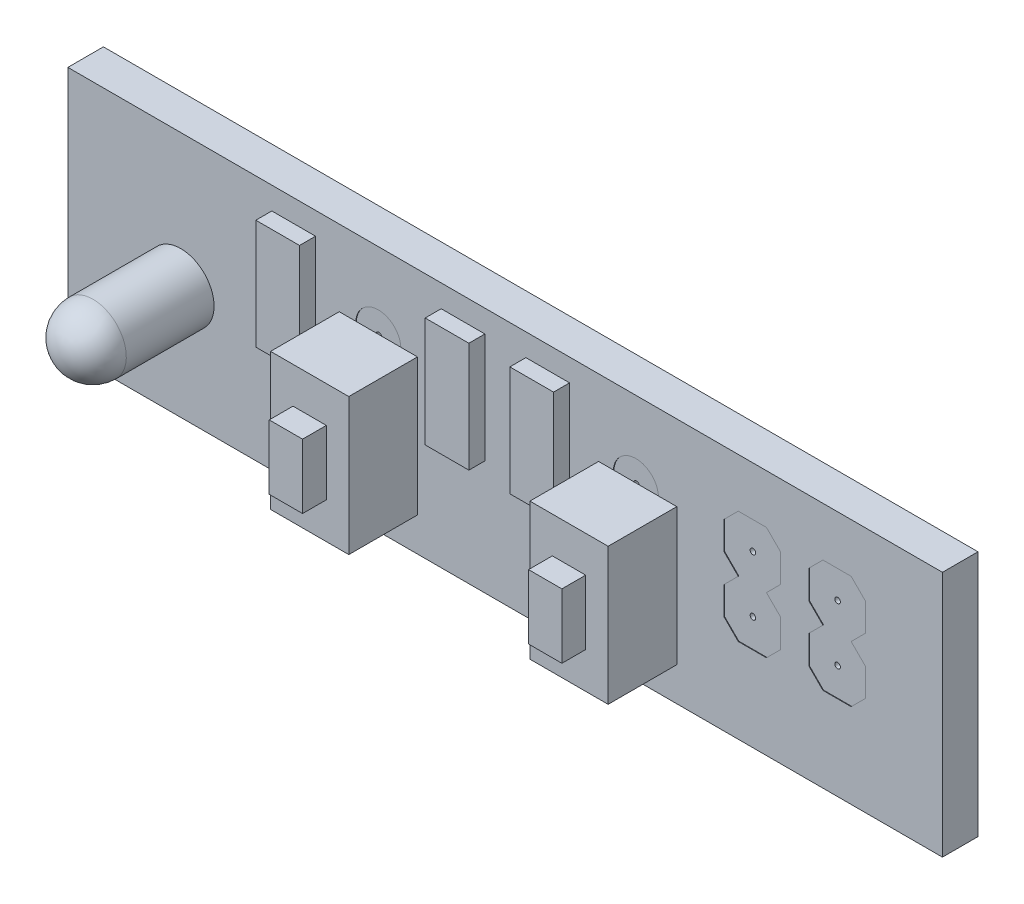
SolidWorks part; units mm, degrees
ref_plane "Front Plane" through (0, 0, 0) normal (0, 0, 1) x (1, 0, 0)
ref_plane "Top Plane" through (0, 0, 0) normal (0, 1, 0) x (1, 0, 0)
ref_plane "Right Plane" through (0, 0, 0) normal (1, 0, 0) x (0, 0, -1)
sketch "Model" plane through (0, 0, 0) normal (0, 0, 1) x (1, 0, 0)
  line L0 (0, 0) -> (39.35, 0)
  line L1 (39.35, 0) -> (39.35, 11.1)
  line L2 (39.35, 11.1) -> (0, 11.1)
  line L3 (0, 11.1) -> (0, 0)
  line L4 (26.7811, 0.4445) -> (26.7811, 0.9525)
  line L5 (26.7811, 0.4445) -> (26.2731, 0.4445)
  line L6 (26.7811, 2.2225) -> (26.7811, 2.7305)
  line L7 (26.7811, 2.7305) -> (26.2731, 2.7305)
  line L8 (25.0031, 2.7305) -> (24.4951, 2.7305)
  line L9 (24.4951, 2.7305) -> (24.4951, 2.2225)
  line L10 (24.4951, 0.9525) -> (24.4951, 0.4445)
  line L11 (24.4951, 0.4445) -> (25.0031, 0.4445)
  line L12 (15.113, 0.4445) -> (15.113, 0.9525)
  line L13 (15.113, 0.4445) -> (14.605, 0.4445)
  line L14 (15.113, 2.2225) -> (15.113, 2.7305)
  line L15 (15.113, 2.7305) -> (14.605, 2.7305)
  line L16 (13.335, 2.7305) -> (12.827, 2.7305)
  line L17 (12.827, 2.7305) -> (12.827, 2.2225)
  line L18 (12.827, 0.9525) -> (12.827, 0.4445)
  line L19 (12.827, 0.4445) -> (13.335, 0.4445)
  line L20 (26.7018, 6.477) -> (26.7018, 6.985)
  line L21 (26.7018, 6.477) -> (26.1938, 6.477)
  line L22 (26.7018, 8.255) -> (26.7018, 8.763)
  line L23 (26.7018, 8.763) -> (26.1938, 8.763)
  line L24 (24.9238, 8.763) -> (24.4158, 8.763)
  line L25 (24.4158, 8.763) -> (24.4158, 8.255)
  line L26 (24.4158, 6.985) -> (24.4158, 6.477)
  line L27 (24.4158, 6.477) -> (24.9238, 6.477)
  line L28 (15.113, 6.477) -> (15.113, 6.985)
  line L29 (15.113, 6.477) -> (14.605, 6.477)
  line L30 (15.113, 8.255) -> (15.113, 8.763)
  line L31 (15.113, 8.763) -> (14.605, 8.763)
  line L32 (13.335, 8.763) -> (12.827, 8.763)
  line L33 (12.827, 8.763) -> (12.827, 8.255)
  line L34 (12.827, 6.985) -> (12.827, 6.477)
  line L35 (12.827, 6.477) -> (13.335, 6.477)
  line L36 (29.5275, 4.445) -> (29.5275, 5.715)
  line L37 (29.5275, 5.715) -> (30.1625, 6.35)
  line L38 (30.1625, 6.35) -> (31.4325, 6.35)
  line L39 (31.4325, 6.35) -> (32.0675, 5.715)
  line L40 (30.1625, 3.81) -> (31.4325, 3.81)
  line L41 (29.5275, 4.445) -> (30.1625, 3.81)
  line L42 (31.4325, 3.81) -> (32.0675, 4.445)
  line L43 (32.0675, 5.715) -> (32.0675, 4.445)
  line L44 (30.1625, 6.35) -> (29.5275, 6.985)
  line L45 (29.5275, 6.985) -> (29.5275, 8.255)
  line L46 (29.5275, 8.255) -> (30.1625, 8.89)
  line L47 (30.1625, 8.89) -> (31.4325, 8.89)
  line L48 (31.4325, 8.89) -> (32.0675, 8.255)
  line L49 (32.0675, 8.255) -> (32.0675, 6.985)
  line L50 (32.0675, 6.985) -> (31.4325, 6.35)
  line L51 (33.3375, 4.445) -> (33.3375, 5.715)
  line L52 (33.3375, 5.715) -> (33.9725, 6.35)
  line L53 (33.9725, 6.35) -> (35.2425, 6.35)
  line L54 (35.2425, 6.35) -> (35.8775, 5.715)
  line L55 (33.9725, 3.81) -> (35.2425, 3.81)
  line L56 (33.3375, 4.445) -> (33.9725, 3.81)
  line L57 (35.2425, 3.81) -> (35.8775, 4.445)
  line L58 (35.8775, 5.715) -> (35.8775, 4.445)
  line L59 (33.9725, 6.35) -> (33.3375, 6.985)
  line L60 (33.3375, 6.985) -> (33.3375, 8.255)
  line L61 (33.3375, 8.255) -> (33.9725, 8.89)
  line L62 (33.9725, 8.89) -> (35.2425, 8.89)
  line L63 (35.2425, 8.89) -> (35.8775, 8.255)
  line L64 (35.8775, 8.255) -> (35.8775, 6.985)
  line L65 (35.8775, 6.985) -> (35.2425, 6.35)
  line L66 (3.5052, 6.35) -> (3.5052, 3.81)
  line L69 (9.177, 5.147) -> (9.177, 10.093)
  line L70 (9.177, 10.093) -> (11.143, 10.093)
  line L71 (11.143, 10.093) -> (11.143, 5.147)
  line L72 (11.143, 5.147) -> (9.177, 5.147)
  line L75 (18.763, 10.093) -> (18.763, 5.147)
  line L76 (18.763, 5.147) -> (16.797, 5.147)
  line L77 (16.797, 5.147) -> (16.797, 10.093)
  line L78 (16.797, 10.093) -> (18.763, 10.093)
  line L79 (22.4028, 8.5725) -> (22.4028, 6.6548)
  line L80 (20.7772, 8.5725) -> (20.7772, 6.6548)
  line L81 (20.607, 5.147) -> (20.607, 10.093)
  line L82 (20.607, 10.093) -> (22.573, 10.093)
  line L83 (22.573, 10.093) -> (22.573, 5.147)
  line L84 (22.573, 5.147) -> (20.607, 5.147)
  arc A0 (26.8192, 0.9525) -> (26.743, 0.9525) centre (26.7811, 0.9525) ccw
  arc A1 (26.743, 0.4445) -> (26.8192, 0.4445) centre (26.7811, 0.4445) ccw
  arc A2 (26.2731, 0.4826) -> (26.2731, 0.4064) centre (26.2731, 0.4445) ccw
  arc A3 (26.7811, 0.4064) -> (26.7811, 0.4826) centre (26.7811, 0.4445) ccw
  arc A4 (26.8192, 2.7305) -> (26.743, 2.7305) centre (26.7811, 2.7305) ccw
  arc A5 (26.743, 2.2225) -> (26.8192, 2.2225) centre (26.7811, 2.2225) ccw
  arc A6 (26.2731, 2.7686) -> (26.2731, 2.6924) centre (26.2731, 2.7305) ccw
  arc A7 (26.7811, 2.6924) -> (26.7811, 2.7686) centre (26.7811, 2.7305) ccw
  arc A8 (24.4951, 2.7686) -> (24.4951, 2.6924) centre (24.4951, 2.7305) ccw
  arc A9 (25.0031, 2.6924) -> (25.0031, 2.7686) centre (25.0031, 2.7305) ccw
  arc A10 (24.457, 2.2225) -> (24.5332, 2.2225) centre (24.4951, 2.2225) ccw
  arc A11 (24.5332, 2.7305) -> (24.457, 2.7305) centre (24.4951, 2.7305) ccw
  arc A12 (24.457, 0.4445) -> (24.5332, 0.4445) centre (24.4951, 0.4445) ccw
  arc A13 (24.5332, 0.9525) -> (24.457, 0.9525) centre (24.4951, 0.9525) ccw
  arc A14 (25.0031, 0.4064) -> (25.0031, 0.4826) centre (25.0031, 0.4445) ccw
  arc A15 (24.4951, 0.4826) -> (24.4951, 0.4064) centre (24.4951, 0.4445) ccw
  circle A16 centre (25.6381, 1.5875) radius 1.016
  arc A17 (15.1511, 0.9525) -> (15.0749, 0.9525) centre (15.113, 0.9525) ccw
  arc A18 (15.0749, 0.4445) -> (15.1511, 0.4445) centre (15.113, 0.4445) ccw
  arc A19 (14.605, 0.4826) -> (14.605, 0.4064) centre (14.605, 0.4445) ccw
  arc A20 (15.113, 0.4064) -> (15.113, 0.4826) centre (15.113, 0.4445) ccw
  arc A21 (15.1511, 2.7305) -> (15.0749, 2.7305) centre (15.113, 2.7305) ccw
  arc A22 (15.0749, 2.2225) -> (15.1511, 2.2225) centre (15.113, 2.2225) ccw
  arc A23 (14.605, 2.7686) -> (14.605, 2.6924) centre (14.605, 2.7305) ccw
  arc A24 (15.113, 2.6924) -> (15.113, 2.7686) centre (15.113, 2.7305) ccw
  arc A25 (12.827, 2.7686) -> (12.827, 2.6924) centre (12.827, 2.7305) ccw
  arc A26 (13.335, 2.6924) -> (13.335, 2.7686) centre (13.335, 2.7305) ccw
  arc A27 (12.7889, 2.2225) -> (12.8651, 2.2225) centre (12.827, 2.2225) ccw
  arc A28 (12.8651, 2.7305) -> (12.7889, 2.7305) centre (12.827, 2.7305) ccw
  arc A29 (12.7889, 0.4445) -> (12.8651, 0.4445) centre (12.827, 0.4445) ccw
  arc A30 (12.8651, 0.9525) -> (12.7889, 0.9525) centre (12.827, 0.9525) ccw
  arc A31 (13.335, 0.4064) -> (13.335, 0.4826) centre (13.335, 0.4445) ccw
  arc A32 (12.827, 0.4826) -> (12.827, 0.4064) centre (12.827, 0.4445) ccw
  circle A33 centre (13.97, 1.5875) radius 1.016
  arc A34 (26.7399, 6.985) -> (26.6637, 6.985) centre (26.7018, 6.985) ccw
  arc A35 (26.6637, 6.477) -> (26.7399, 6.477) centre (26.7018, 6.477) ccw
  arc A36 (26.1938, 6.5151) -> (26.1938, 6.4389) centre (26.1938, 6.477) ccw
  arc A37 (26.7018, 6.4389) -> (26.7018, 6.5151) centre (26.7018, 6.477) ccw
  arc A38 (26.7399, 8.763) -> (26.6637, 8.763) centre (26.7018, 8.763) ccw
  arc A39 (26.6637, 8.255) -> (26.7399, 8.255) centre (26.7018, 8.255) ccw
  arc A40 (26.1938, 8.8011) -> (26.1938, 8.7249) centre (26.1938, 8.763) ccw
  arc A41 (26.7018, 8.7249) -> (26.7018, 8.8011) centre (26.7018, 8.763) ccw
  arc A42 (24.4158, 8.8011) -> (24.4158, 8.7249) centre (24.4158, 8.763) ccw
  arc A43 (24.9238, 8.7249) -> (24.9238, 8.8011) centre (24.9238, 8.763) ccw
  arc A44 (24.3777, 8.255) -> (24.4539, 8.255) centre (24.4158, 8.255) ccw
  arc A45 (24.4539, 8.763) -> (24.3777, 8.763) centre (24.4158, 8.763) ccw
  arc A46 (24.3777, 6.477) -> (24.4539, 6.477) centre (24.4158, 6.477) ccw
  arc A47 (24.4539, 6.985) -> (24.3777, 6.985) centre (24.4158, 6.985) ccw
  arc A48 (24.9238, 6.4389) -> (24.9238, 6.5151) centre (24.9238, 6.477) ccw
  arc A49 (24.4158, 6.5151) -> (24.4158, 6.4389) centre (24.4158, 6.477) ccw
  circle A50 centre (25.5587, 7.62) radius 1.016
  arc A51 (15.1511, 6.985) -> (15.0749, 6.985) centre (15.113, 6.985) ccw
  arc A52 (15.0749, 6.477) -> (15.1511, 6.477) centre (15.113, 6.477) ccw
  arc A53 (14.605, 6.5151) -> (14.605, 6.4389) centre (14.605, 6.477) ccw
  arc A54 (15.113, 6.4389) -> (15.113, 6.5151) centre (15.113, 6.477) ccw
  arc A55 (15.1511, 8.763) -> (15.0749, 8.763) centre (15.113, 8.763) ccw
  arc A56 (15.0749, 8.255) -> (15.1511, 8.255) centre (15.113, 8.255) ccw
  arc A57 (14.605, 8.8011) -> (14.605, 8.7249) centre (14.605, 8.763) ccw
  arc A58 (15.113, 8.7249) -> (15.113, 8.8011) centre (15.113, 8.763) ccw
  arc A59 (12.827, 8.8011) -> (12.827, 8.7249) centre (12.827, 8.763) ccw
  arc A60 (13.335, 8.7249) -> (13.335, 8.8011) centre (13.335, 8.763) ccw
  arc A61 (12.7889, 8.255) -> (12.8651, 8.255) centre (12.827, 8.255) ccw
  arc A62 (12.8651, 8.763) -> (12.7889, 8.763) centre (12.827, 8.763) ccw
  arc A63 (12.7889, 6.477) -> (12.8651, 6.477) centre (12.827, 6.477) ccw
  arc A64 (12.8651, 6.985) -> (12.7889, 6.985) centre (12.827, 6.985) ccw
  arc A65 (13.335, 6.4389) -> (13.335, 6.5151) centre (13.335, 6.477) ccw
  arc A66 (12.827, 6.5151) -> (12.827, 6.4389) centre (12.827, 6.477) ccw
  circle A67 centre (13.97, 7.62) radius 1.016
  arc A68 (29.5656, 5.715) -> (29.4894, 5.715) centre (29.5275, 5.715) ccw
  arc A69 (29.4894, 4.445) -> (29.5656, 4.445) centre (29.5275, 4.445) ccw
  arc A70 (30.1894, 6.3231) -> (30.1356, 6.3769) centre (30.1625, 6.35) ccw
  arc A71 (29.5006, 5.7419) -> (29.5544, 5.6881) centre (29.5275, 5.715) ccw
  arc A72 (31.4325, 6.3119) -> (31.4325, 6.3881) centre (31.4325, 6.35) ccw
  arc A73 (30.1625, 6.3881) -> (30.1625, 6.3119) centre (30.1625, 6.35) ccw
  arc A74 (32.0406, 5.6881) -> (32.0944, 5.7419) centre (32.0675, 5.715) ccw
  arc A75 (31.4594, 6.3769) -> (31.4056, 6.3231) centre (31.4325, 6.35) ccw
  arc A76 (31.4325, 3.7719) -> (31.4325, 3.8481) centre (31.4325, 3.81) ccw
  arc A77 (30.1625, 3.8481) -> (30.1625, 3.7719) centre (30.1625, 3.81) ccw
  arc A78 (30.1356, 3.7831) -> (30.1894, 3.8369) centre (30.1625, 3.81) ccw
  arc A79 (29.5544, 4.4719) -> (29.5006, 4.4181) centre (29.5275, 4.445) ccw
  arc A80 (32.0944, 4.4181) -> (32.0406, 4.4719) centre (32.0675, 4.445) ccw
  arc A81 (31.4056, 3.8369) -> (31.4594, 3.7831) centre (31.4325, 3.81) ccw
  arc A82 (32.0294, 4.445) -> (32.1056, 4.445) centre (32.0675, 4.445) ccw
  arc A83 (32.1056, 5.715) -> (32.0294, 5.715) centre (32.0675, 5.715) ccw
  arc A84 (29.5544, 7.0119) -> (29.5006, 6.9581) centre (29.5275, 6.985) ccw
  arc A85 (30.1356, 6.3231) -> (30.1894, 6.3769) centre (30.1625, 6.35) ccw
  arc A86 (29.5656, 8.255) -> (29.4894, 8.255) centre (29.5275, 8.255) ccw
  arc A87 (29.4894, 6.985) -> (29.5656, 6.985) centre (29.5275, 6.985) ccw
  arc A88 (30.1894, 8.8631) -> (30.1356, 8.9169) centre (30.1625, 8.89) ccw
  arc A89 (29.5006, 8.2819) -> (29.5544, 8.2281) centre (29.5275, 8.255) ccw
  arc A90 (31.4325, 8.8519) -> (31.4325, 8.9281) centre (31.4325, 8.89) ccw
  arc A91 (30.1625, 8.9281) -> (30.1625, 8.8519) centre (30.1625, 8.89) ccw
  arc A92 (32.0406, 8.2281) -> (32.0944, 8.2819) centre (32.0675, 8.255) ccw
  arc A93 (31.4594, 8.9169) -> (31.4056, 8.8631) centre (31.4325, 8.89) ccw
  arc A94 (32.0294, 6.985) -> (32.1056, 6.985) centre (32.0675, 6.985) ccw
  arc A95 (32.1056, 8.255) -> (32.0294, 8.255) centre (32.0675, 8.255) ccw
  arc A96 (31.4056, 6.3769) -> (31.4594, 6.3231) centre (31.4325, 6.35) ccw
  arc A97 (32.0944, 6.9581) -> (32.0406, 7.0119) centre (32.0675, 6.985) ccw
  arc A98 (33.3756, 5.715) -> (33.2994, 5.715) centre (33.3375, 5.715) ccw
  arc A99 (33.2994, 4.445) -> (33.3756, 4.445) centre (33.3375, 4.445) ccw
  arc A100 (33.9994, 6.3231) -> (33.9456, 6.3769) centre (33.9725, 6.35) ccw
  arc A101 (33.3106, 5.7419) -> (33.3644, 5.6881) centre (33.3375, 5.715) ccw
  arc A102 (35.2425, 6.3119) -> (35.2425, 6.3881) centre (35.2425, 6.35) ccw
  arc A103 (33.9725, 6.3881) -> (33.9725, 6.3119) centre (33.9725, 6.35) ccw
  arc A104 (35.8506, 5.6881) -> (35.9044, 5.7419) centre (35.8775, 5.715) ccw
  arc A105 (35.2694, 6.3769) -> (35.2156, 6.3231) centre (35.2425, 6.35) ccw
  arc A106 (35.2425, 3.7719) -> (35.2425, 3.8481) centre (35.2425, 3.81) ccw
  arc A107 (33.9725, 3.8481) -> (33.9725, 3.7719) centre (33.9725, 3.81) ccw
  arc A108 (33.9456, 3.7831) -> (33.9994, 3.8369) centre (33.9725, 3.81) ccw
  arc A109 (33.3644, 4.4719) -> (33.3106, 4.4181) centre (33.3375, 4.445) ccw
  arc A110 (35.9044, 4.4181) -> (35.8506, 4.4719) centre (35.8775, 4.445) ccw
  arc A111 (35.2156, 3.8369) -> (35.2694, 3.7831) centre (35.2425, 3.81) ccw
  arc A112 (35.8394, 4.445) -> (35.9156, 4.445) centre (35.8775, 4.445) ccw
  arc A113 (35.9156, 5.715) -> (35.8394, 5.715) centre (35.8775, 5.715) ccw
  arc A114 (33.3644, 7.0119) -> (33.3106, 6.9581) centre (33.3375, 6.985) ccw
  arc A115 (33.9456, 6.3231) -> (33.9994, 6.3769) centre (33.9725, 6.35) ccw
  arc A116 (33.3756, 8.255) -> (33.2994, 8.255) centre (33.3375, 8.255) ccw
  arc A117 (33.2994, 6.985) -> (33.3756, 6.985) centre (33.3375, 6.985) ccw
  arc A118 (33.9994, 8.8631) -> (33.9456, 8.9169) centre (33.9725, 8.89) ccw
  arc A119 (33.3106, 8.2819) -> (33.3644, 8.2281) centre (33.3375, 8.255) ccw
  arc A120 (35.2425, 8.8519) -> (35.2425, 8.9281) centre (35.2425, 8.89) ccw
  arc A121 (33.9725, 8.9281) -> (33.9725, 8.8519) centre (33.9725, 8.89) ccw
  arc A122 (35.8506, 8.2281) -> (35.9044, 8.2819) centre (35.8775, 8.255) ccw
  arc A123 (35.2694, 8.9169) -> (35.2156, 8.8631) centre (35.2425, 8.89) ccw
  arc A124 (35.8394, 6.985) -> (35.9156, 6.985) centre (35.8775, 6.985) ccw
  arc A125 (35.9156, 8.255) -> (35.8394, 8.255) centre (35.8775, 8.255) ccw
  arc A126 (35.2156, 6.3769) -> (35.2694, 6.3231) centre (35.2425, 6.35) ccw
  arc A127 (35.9044, 6.9581) -> (35.8506, 7.0119) centre (35.8775, 6.985) ccw
  arc A128 (3.4417, 3.81) -> (3.5687, 3.81) centre (3.5052, 3.81) ccw
  arc A129 (3.5687, 6.35) -> (3.4417, 6.35) centre (3.5052, 6.35) ccw
  arc A130 (6.2508, 4.1044) -> (6.604, 5.08) centre (5.0796, 5.0801) ccw
  arc A131 (6.2215, 4.1288) -> (6.2801, 4.08) centre (6.2508, 4.1044) ccw
  arc A132 (6.6421, 5.08) -> (6.5659, 5.08) centre (6.604, 5.08) ccw
  arc A133 (6.604, 5.08) -> (6.2191, 6.0925) centre (5.0801, 5.0801) ccw
  arc A134 (6.5659, 5.08) -> (6.6421, 5.08) centre (6.604, 5.08) ccw
  arc A135 (6.2476, 6.1178) -> (6.1906, 6.0672) centre (6.2191, 6.0925) ccw
  arc A136 (3.556, 5.08) -> (3.9229, 4.0882) centre (5.0803, 5.0801) ccw
  arc A137 (3.5941, 5.08) -> (3.5179, 5.08) centre (3.556, 5.08) ccw
  arc A138 (3.894, 4.0634) -> (3.9518, 4.113) centre (3.9229, 4.0882) ccw
  arc A139 (3.9092, 6.0556) -> (3.556, 5.08) centre (5.0804, 5.0799) ccw
  arc A140 (3.9385, 6.0312) -> (3.8799, 6.08) centre (3.9092, 6.0556) ccw
  arc A141 (3.5179, 5.08) -> (3.5941, 5.08) centre (3.556, 5.08) ccw
  arc A142 (3.8399, 4.1942) -> (5.08, 3.556) centre (5.0801, 5.08) ccw
  arc A143 (3.8709, 4.2163) -> (3.8089, 4.1721) centre (3.8399, 4.1942) ccw
  arc A144 (5.08, 3.5179) -> (5.08, 3.5941) centre (5.08, 3.556) ccw
  arc A145 (5.08, 3.556) -> (6.2992, 4.1656) centre (5.0801, 5.0798) ccw
  arc A146 (5.08, 3.5941) -> (5.08, 3.5179) centre (5.08, 3.556) ccw
  arc A147 (6.3297, 4.1427) -> (6.2687, 4.1885) centre (6.2992, 4.1656) ccw
  arc A148 (5.08, 6.604) -> (3.877, 6.0156) centre (5.0799, 5.0803) ccw
  arc A149 (5.08, 6.5659) -> (5.08, 6.6421) centre (5.08, 6.604) ccw
  arc A150 (3.8469, 6.039) -> (3.9071, 5.9922) centre (3.877, 6.0156) ccw
  arc A151 (6.283, 6.0156) -> (5.08, 6.604) centre (5.0801, 5.0803) ccw
  arc A152 (6.2529, 5.9922) -> (6.3131, 6.039) centre (6.283, 6.0156) ccw
  arc A153 (5.08, 6.6421) -> (5.08, 6.5659) centre (5.08, 6.604) ccw
  arc A154 (5.08, 4.445) -> (5.715, 5.08) centre (5.08, 5.08) ccw
  arc A155 (5.08, 4.4831) -> (5.08, 4.4069) centre (5.08, 4.445) ccw
  arc A156 (5.7531, 5.08) -> (5.6769, 5.08) centre (5.715, 5.08) ccw
  arc A157 (5.08, 4.064) -> (6.096, 5.08) centre (5.08, 5.08) ccw
  arc A158 (5.08, 4.1021) -> (5.08, 4.0259) centre (5.08, 4.064) ccw
  arc A159 (6.1341, 5.08) -> (6.0579, 5.08) centre (6.096, 5.08) ccw
  arc A160 (5.08, 5.715) -> (4.445, 5.08) centre (5.08, 5.08) ccw
  arc A161 (5.08, 5.6769) -> (5.08, 5.7531) centre (5.08, 5.715) ccw
  arc A162 (4.4069, 5.08) -> (4.4831, 5.08) centre (4.445, 5.08) ccw
  arc A163 (5.08, 6.096) -> (4.064, 5.08) centre (5.08, 5.08) ccw
  arc A164 (5.08, 6.0579) -> (5.08, 6.1341) centre (5.08, 6.096) ccw
  arc A165 (4.0259, 5.08) -> (4.1021, 5.08) centre (4.064, 5.08) ccw
  arc A166 (3.519, 3.7791) -> (5.08, 3.048) centre (5.0799, 5.0798) ccw
  arc A167 (3.5678, 3.8198) -> (3.4702, 3.7384) centre (3.519, 3.7791) ccw
  arc A168 (5.08, 2.9845) -> (5.08, 3.1115) centre (5.08, 3.048) ccw
  arc A169 (5.08, 3.048) -> (6.8729, 4.1238) centre (5.08, 5.0799) ccw
  arc A170 (5.08, 3.1115) -> (5.08, 2.9845) centre (5.08, 3.048) ccw
  arc A171 (6.9289, 4.0939) -> (6.8169, 4.1537) centre (6.8729, 4.1238) ccw
  arc A172 (5.08, 7.112) -> (3.5288, 6.3926) centre (5.08, 5.0799) ccw
  arc A173 (5.08, 7.0485) -> (5.08, 7.1755) centre (5.08, 7.112) ccw
  arc A174 (3.4803, 6.4336) -> (3.5773, 6.3516) centre (3.5288, 6.3926) ccw
  arc A175 (6.8443, 6.0882) -> (5.08, 7.112) centre (5.0799, 5.0797) ccw
  arc A176 (6.7892, 6.0567) -> (6.8994, 6.1197) centre (6.8443, 6.0882) ccw
  arc A177 (5.08, 7.1755) -> (5.08, 7.0485) centre (5.08, 7.112) ccw
  arc A178 (6.8691, 4.1166) -> (7.112, 5.08) centre (5.0797, 5.0801) ccw
  arc A179 (6.8132, 4.1467) -> (6.925, 4.0865) centre (6.8691, 4.1166) ccw
  arc A180 (7.1755, 5.08) -> (7.0485, 5.08) centre (7.112, 5.08) ccw
  arc A181 (7.112, 5.08) -> (6.8106, 6.145) centre (5.08, 5.0801) ccw
  arc A182 (7.0485, 5.08) -> (7.1755, 5.08) centre (7.112, 5.08) ccw
  arc A183 (6.8647, 6.1783) -> (6.7565, 6.1117) centre (6.8106, 6.145) ccw
  arc A201 (18.7757, 10.093) -> (18.7503, 10.093) centre (18.763, 10.093) ccw
  arc A204 (16.8097, 10.093) -> (16.7843, 10.093) centre (16.797, 10.093) ccw
  arc A206 (18.763, 10.0803) -> (18.763, 10.1057) centre (18.763, 10.093) ccw
  arc A207 (16.797, 10.1057) -> (16.797, 10.0803) centre (16.797, 10.093) ccw
  arc A208 (22.3647, 6.6548) -> (22.4409, 6.6548) centre (22.4028, 6.6548) ccw
  arc A209 (22.4409, 8.5725) -> (22.3647, 8.5725) centre (22.4028, 8.5725) ccw
  arc A210 (20.7391, 6.6548) -> (20.8153, 6.6548) centre (20.7772, 6.6548) ccw
  arc A211 (20.8153, 8.5725) -> (20.7391, 8.5725) centre (20.7772, 8.5725) ccw
  arc A212 (20.6197, 10.093) -> (20.5943, 10.093) centre (20.607, 10.093) ccw
  arc A213 (20.5943, 5.147) -> (20.6197, 5.147) centre (20.607, 5.147) ccw
  arc A214 (22.573, 10.0803) -> (22.573, 10.1057) centre (22.573, 10.093) ccw
  arc A215 (20.607, 10.1057) -> (20.607, 10.0803) centre (20.607, 10.093) ccw
  arc A216 (22.5603, 5.147) -> (22.5857, 5.147) centre (22.573, 5.147) ccw
  arc A217 (22.5857, 10.093) -> (22.5603, 10.093) centre (22.573, 10.093) ccw
  arc A218 (20.607, 5.1597) -> (20.607, 5.1343) centre (20.607, 5.147) ccw
  arc A219 (22.573, 5.1343) -> (22.573, 5.1597) centre (22.573, 5.147) ccw
  dimension "D3" = 11.6681
  dimension "D1" = 11.1
  dimension "D2" = 39.35
  dimension "D4" = 5.0796
sketch "Sketch2" plane through (0, 0, 0) normal (0, 0, 1) x (1, 0, 0)
  line L1 (0, 0) -> (39.35, 0)
  line L2 (0, 0) -> (0, 11.1)
  line L3 (0, 11.1) -> (39.35, 11.1)
  line L4 (39.35, 0) -> (39.35, 11.1)
extrude "Boss-Extrude1" add sketch "Sketch2" against normal blind 1.6
sketch "Sketch3" plane through (0, 0, 0) normal (0, 0, 1) x (1, 0, 0)
  line L1 (9.177, 10.093) -> (11.143, 10.093)
  line L2 (9.177, 10.093) -> (9.177, 5.147)
  line L3 (9.177, 5.147) -> (11.143, 5.147)
  line L4 (11.143, 10.093) -> (11.143, 5.147)
  line L5 (16.797, 10.093) -> (18.763, 10.093)
  line L6 (16.797, 10.093) -> (16.797, 5.147)
  line L7 (16.797, 5.147) -> (18.763, 5.147)
  line L8 (18.763, 10.093) -> (18.763, 5.147)
  line L9 (20.607, 10.093) -> (22.573, 10.093)
  line L10 (20.607, 10.093) -> (20.607, 5.147)
  line L11 (20.607, 5.147) -> (22.573, 5.147)
  line L12 (22.573, 10.093) -> (22.573, 5.147)
extrude "Boss-Extrude2" add sketch "Sketch3" along normal blind 0.72
sketch "Sketch4" plane through (0, 0, 0) normal (0, 0, 1) x (1, 0, 0)
  circle A0 centre (13.97, 1.5875) radius 1.016
  circle A1 centre (13.97, 1.5875) radius 0.13
  circle A2 centre (13.97, 7.62) radius 1.016
  circle A3 centre (13.97, 7.62) radius 0.13
  circle A4 centre (25.5587, 7.62) radius 1.016
  circle A5 centre (25.5587, 7.62) radius 0.13
  circle A6 centre (25.6381, 1.5875) radius 1.016
  circle A7 centre (25.6381, 1.5875) radius 0.13
  dimension "D1" = 0.26
extrude "Cut-Extrude1" cut sketch "Sketch4" against normal blind 0.0254 contours A0 A1 | A1 | A6 A7 | A7 | A5 | A4 A5 | A3 | A2 A3 region at (12.9827, 1.5875, 0) region at (13.97, 1.5875, 0) region at (12.9827, 7.62, 0) region at (13.97, 7.62, 0) region at (24.5714, 7.62, 0) region at (25.5587, 7.62, 0) region at (24.6508, 1.5875, 0) region at (25.6381, 1.5875, 0)
extrude "Cut-Extrude2" cut sketch "Sketch4<3>" against normal through all contours A1 | A7 | A5 | A3 region at (13.97, 1.5875, 0) region at (13.97, 7.62, 0) region at (25.5587, 7.62, 0) region at (25.6381, 1.5875, 0)
sketch "Sketch4<3>" plane through (0, 0, 0) normal (0, 0, 1) x (1, 0, 0) same geometry as "Sketch4"
sketch "Sketch5" plane through (0, 0, 0) normal (0, 0, 1) x (1, 0, 0)
  line L0 (29.5275, 6.985) -> (29.5275, 8.255) construction
  line L1 (30.1625, 6.35) -> (29.5275, 6.985) construction
  line L2 (29.5275, 8.255) -> (30.1625, 8.89) construction
  line L3 (30.1625, 8.89) -> (31.4325, 8.89) construction
  line L4 (31.4325, 8.89) -> (32.0675, 8.255) construction
  line L5 (32.0675, 8.255) -> (32.0675, 6.985) construction
  line L6 (32.0675, 6.985) -> (31.4325, 6.35) construction
  line L7 (31.4325, 6.35) -> (32.0675, 5.715) construction
  line L8 (32.0675, 5.715) -> (32.0675, 4.445) construction
  line L9 (29.5275, 5.715) -> (30.1625, 6.35) construction
  line L10 (29.5275, 4.445) -> (29.5275, 5.715) construction
  line L11 (29.5275, 4.445) -> (30.1625, 3.81) construction
  line L12 (30.1625, 3.81) -> (31.4325, 3.81) construction
  line L13 (31.4325, 3.81) -> (32.0675, 4.445) construction
  line L14 (33.3375, 4.445) -> (33.3375, 5.715) construction
  line L15 (33.3375, 5.715) -> (33.9725, 6.35) construction
  line L16 (33.9725, 6.35) -> (33.3375, 6.985) construction
  line L17 (33.3375, 6.985) -> (33.3375, 8.255) construction
  line L18 (33.3375, 8.255) -> (33.9725, 8.89) construction
  line L19 (33.9725, 8.89) -> (35.2425, 8.89) construction
  line L20 (35.2425, 8.89) -> (35.8775, 8.255) construction
  line L21 (35.8775, 8.255) -> (35.8775, 6.985) construction
  line L22 (35.8775, 6.985) -> (35.2425, 6.35) construction
  line L23 (35.2425, 6.35) -> (35.8775, 5.715) construction
  line L24 (35.8775, 5.715) -> (35.8775, 4.445) construction
  line L25 (35.2425, 3.81) -> (35.8775, 4.445) construction
  line L26 (33.9725, 3.81) -> (35.2425, 3.81) construction
  line L27 (33.3375, 4.445) -> (33.9725, 3.81) construction
  line L28 (29.5275, 6.985) -> (29.5275, 8.255)
  line L29 (30.1625, 6.35) -> (29.5275, 6.985)
  line L30 (29.5275, 8.255) -> (30.1625, 8.89)
  line L31 (30.1625, 8.89) -> (31.4325, 8.89)
  line L32 (31.4325, 8.89) -> (32.0675, 8.255)
  line L33 (32.0675, 8.255) -> (32.0675, 6.985)
  line L34 (32.0675, 6.985) -> (31.4325, 6.35)
  line L35 (31.4325, 6.35) -> (32.0675, 5.715)
  line L36 (32.0675, 5.715) -> (32.0675, 4.445)
  line L37 (29.5275, 5.715) -> (30.1625, 6.35)
  line L38 (29.5275, 4.445) -> (29.5275, 5.715)
  line L39 (29.5275, 4.445) -> (30.1625, 3.81)
  line L40 (30.1625, 3.81) -> (31.4325, 3.81)
  line L41 (31.4325, 3.81) -> (32.0675, 4.445)
  line L42 (33.3375, 4.445) -> (33.3375, 5.715)
  line L43 (33.3375, 5.715) -> (33.9725, 6.35)
  line L44 (33.9725, 6.35) -> (33.3375, 6.985)
  line L45 (33.3375, 6.985) -> (33.3375, 8.255)
  line L46 (33.3375, 8.255) -> (33.9725, 8.89)
  line L47 (33.9725, 8.89) -> (35.2425, 8.89)
  line L48 (35.2425, 8.89) -> (35.8775, 8.255)
  line L49 (35.8775, 8.255) -> (35.8775, 6.985)
  line L50 (35.8775, 6.985) -> (35.2425, 6.35)
  line L51 (35.2425, 6.35) -> (35.8775, 5.715)
  line L52 (35.8775, 5.715) -> (35.8775, 4.445)
  line L53 (35.2425, 3.81) -> (35.8775, 4.445)
  line L54 (33.9725, 3.81) -> (35.2425, 3.81)
  line L55 (33.3375, 4.445) -> (33.9725, 3.81)
extrude "Cut-Extrude3" cut sketch "Sketch5" against normal blind 0.0254
sketch "Sketch6" plane through (0, 0, -0.0254) normal (0, 0, 1) x (1, 0, 0)
  line L0 (30.5575, 6.35) -> (31.027, 6.35) construction
  line L1 (30.1625, 6.35) -> (31.4325, 6.35) construction
  line L2 (32.0675, 7.62) -> (33.3375, 7.62) construction
  line L3 (32.0675, 8.255) -> (32.0675, 6.985) construction
  line L4 (33.3375, 6.985) -> (33.3375, 8.255) construction
  line L5 (32.7025, 7.62) -> (32.7025, 6.832) construction
  line L6 (32.0675, 7.62) -> (29.5275, 7.62) construction
  line L7 (29.5275, 6.985) -> (29.5275, 8.255) construction
  circle A0 centre (30.7975, 7.62) radius 0.125
  circle A1 centre (30.7975, 5.08) radius 0.125
  circle A2 centre (34.6075, 5.08) radius 0.125
  circle A3 centre (34.6075, 7.62) radius 0.125
  dimension "D1" = 0.25
extrude "Cut-Extrude4" cut sketch "Sketch6" against normal through all
sketch "Sketch8" plane through (0, 0, 0) normal (0, 0, 1) x (1, 0, 0)
  line L0 (13.97, 7.62) -> (13.97, 1.5875) construction
  line L1 (12.21, 7.6838) -> (15.73, 7.6838)
  line L2 (12.21, 7.6838) -> (12.21, 1.5237)
  line L3 (12.21, 1.5237) -> (15.73, 1.5238)
  line L4 (15.73, 7.6838) -> (15.73, 1.5238)
  line L5 (12.21, 4.6037) -> (15.73, 4.6037) construction
  point P10 (13.97, 4.6037)
  dimension "D1" = 6.16
  dimension "D2" = 3.52
extrude "Boss-Extrude3" add sketch "Sketch8" along normal blind 3.09
sketch "Sketch9" plane through (0, 0, 3.09) normal (0, 0, 1) x (1, 0, 0)
  line L0 (12.21, 4.6037) -> (15.73, 4.6037) construction
  line L1 (13.22, 6.0537) -> (14.72, 6.0537)
  line L2 (13.22, 6.0537) -> (13.22, 3.1538)
  line L3 (13.22, 3.1538) -> (14.72, 3.1538)
  line L4 (14.72, 6.0537) -> (14.72, 3.1538)
  line L5 (12.21, 7.6838) -> (12.21, 1.5237) construction
  line L6 (15.73, 1.5238) -> (15.73, 7.6838) construction
  line L7 (13.97, 4.6037) -> (13.97, 7.0288) construction
  dimension "D1" = 2.9
  dimension "D2" = 1.5
extrude "Boss-Extrude4" add sketch "Sketch9" along normal blind 1.07
pattern_linear "LPattern1" count 2 spacing 11.6681 along (1, 0, 0) of "Boss-Extrude4", "Boss-Extrude3"
ref_plane "Plane1" through (5.0796, 0, 0) normal (-1, 0, 0) x (0, 0, 1)
sketch "Sketch11" plane through (5.0796, 0, 0) normal (-1, 0, 0) x (0, 0, 1)
  line L0 (0, 5.08) -> (11.4487, 5.08) construction
  line L1 (0, 5.715) -> (0, 4.445) construction
  line L2 (0, 5.08) -> (0, 6.58)
  line L3 (0, 6.58) -> (3.95, 6.58)
  line L4 (5.45, 5.08) -> (0, 5.08)
  line L5 (5.45, 5.08) -> (5.45, 0.5291) construction
  arc A0 (3.95, 6.58) -> (5.45, 5.08) centre (3.95, 5.08) cw
  dimension "D1" = 3
  dimension "D2" = 5.45
revolve "Revolve18" add sketch "Sketch11" angle 360 about L0
